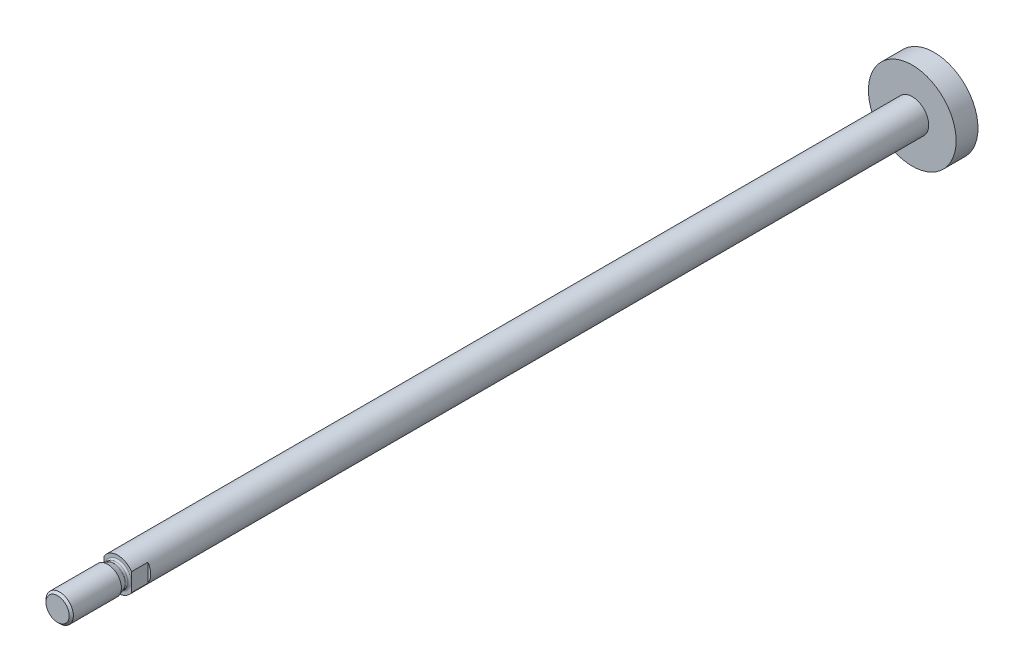
SolidWorks part; units mm, degrees
ref_plane "Front Plane" through (0, 0, 0) normal (0, 0, 1) x (1, 0, 0)
ref_plane "Top Plane" through (0, 0, 0) normal (0, 1, 0) x (1, 0, 0)
ref_plane "Right Plane" through (0, 0, 0) normal (1, 0, 0) x (0, 0, -1)
sketch "Sketch1" plane through (0, 0, 0) normal (1, 0, 0) x (0, 0, -1)
  line L0 (-8, 0) -> (-8, 6)
  line L1 (-8, 6) -> (282, 6)
  line L2 (282, 6) -> (282, 16)
  line L3 (282, 16) -> (290, 16)
  line L4 (290, 16) -> (290, 0)
  line L5 (290, 0) -> (-8, 0)
  line L6 (290, 0) -> (-8, 0) construction
revolve "Revolve1" add sketch "Sketch1" angle 360 about L6 reverse direction yes
sketch "Sketch2" plane through (0, 0, 0) normal (1, 0, 0) x (0, 0, -1)
  line L0 (-30, 0) -> (-30, 4.233)
  line L1 (-30, 4.233) -> (-29.233, 5)
  line L2 (-29.233, 5) -> (-11.698, 5)
  line L3 (-11.698, 5) -> (-9.5994, 4.2362)
  line L4 (-9.3942, 4.2) -> (-8.6, 4.2)
  line L5 (-8, 4.8) -> (-8, 5)
  line L6 (-8, 5) -> (-7, 5)
  line L7 (-7, 5) -> (-7, 0)
  line L8 (-7, 0) -> (-30, 0)
  line L9 (-7, 0) -> (-30, 0) construction
  arc A0 (-9.5994, 4.2362) -> (-9.3942, 4.2) centre (-9.3942, 4.8) ccw
  arc A1 (-8.6, 4.2) -> (-8, 4.8) centre (-8.6, 4.8) ccw
revolve "Revolve2" add sketch "Sketch2" angle 360 about L9 reverse direction yes
cosmetic thread "Cosmetic Thread1" parameters "D1"=18.302, "D2"=8.466
ref_plane "Plane4" through (0, 0, 8) normal (0, 0, 1) x (1, 0, 0)
ref_plane "Plane5" through (0, 0, 2) normal (0, 0, 1) x (1, 0, 0)
sketch "Sketch3" plane through (0, 0, 2) normal (0, 0, 1) x (1, 0, 0)
  line L0 (-10, 20) -> (-10, -10)
  line L1 (-10, -10) -> (-5, -10)
  line L2 (-5, -10) -> (-5, 10)
  line L3 (-5, 10) -> (5, 10)
  line L4 (5, 10) -> (5, -10)
  line L5 (5, -10) -> (10, -10)
  line L6 (10, -10) -> (10, 20)
  line L7 (10, 20) -> (-10, 20)
extrude "Cut-Extrude1" cut sketch "Sketch3" along normal blind 7
ref_plane "Plane6" through (0, 0, -579.5) normal (0, 0, 1) x (1, 0, 0)
ref_plane "Plane7" through (0, 0, 22) normal (0, 0, 1) x (1, 0, 0)
ref_plane "Plane8" through (0, 0, 17) normal (0, 0, 1) x (1, 0, 0)
ref_plane "FDT_KSAUFSATZ XY" through (0, 0, 17) normal (0, 0, 1) x (1, 0, 0)
ref_plane "FDT_KSAUFSATZ XZ" through (0, 0, 0) normal (0, 1, 0) x (1, 0, 0)
ref_plane "FDT_KSAUFSATZ YZ" through (0, 0, 0) normal (-1, 0, 0) x (0, 0, 1)
ref_axis "FDT_KSAUFSATZ X" through (80.9, 0, 17) along (-1, 0, 0)
ref_axis "FDT_KSAUFSATZ Y" through (0, 50, 17) along (0, -1, 0)
ref_axis "FDT_KSAUFSATZ Z" through (0, 0, 80.9) along (0, 0, -1)
sketch3d "FDT_KSAUFSATZ"
  point P0 (0, 0, 17)
ref_plane "FDT_NUT XY" through (0, 0, 17) normal (0, 0, 1) x (1, 0, 0)
ref_plane "FDT_NUT XZ" through (0, 0, 0) normal (0, 1, 0) x (1, 0, 0)
ref_plane "FDT_NUT YZ" through (0, 0, 0) normal (-1, 0, 0) x (0, 0, 1)
ref_axis "FDT_NUT X" through (80.9, 0, 17) along (-1, 0, 0)
ref_axis "FDT_NUT Y" through (0, 50, 17) along (0, -1, 0)
ref_axis "FDT_NUT Z" through (0, 0, 80.9) along (0, 0, -1)
sketch3d "FDT_NUT"
  point P0 (0, 0, 17)
ref_plane "KS XY" through (0, 0, 0) normal (0, 0, -1) x (-1, 0, 0)
ref_plane "KS XZ" through (0, 0, 0) normal (0, 1, 0) x (1, 0, 0)
ref_plane "KS YZ" through (0, 0, 0) normal (1, 0, 0) x (0, 0, -1)
ref_axis "KS X" through (-80.9, 0, 0) along (1, 0, 0)
ref_axis "KS Y" through (0, 50, 0) along (0, -1, 0)
ref_axis "KS Z" through (0, 0, -80.9) along (0, 0, 1)
sketch3d "KS"
  point P0 (0, 0, 0)
ref_plane "NUT1 XY" through (0, 0, 22) normal (0, 0, 1) x (1, 0, 0)
ref_plane "NUT1 XZ" through (0, 0, 0) normal (0, -1, 0) x (-1, 0, 0)
ref_plane "NUT1 YZ" through (0, 0, 0) normal (1, 0, 0) x (0, 0, -1)
ref_axis "NUT1 X" through (-80.9, 0, 22) along (1, 0, 0)
ref_axis "NUT1 Y" through (0, -50, 22) along (0, 1, 0)
ref_axis "NUT1 Z" through (0, 0, 80.9) along (0, 0, -1)
sketch3d "NUT1"
  point P0 (0, 0, 22)
